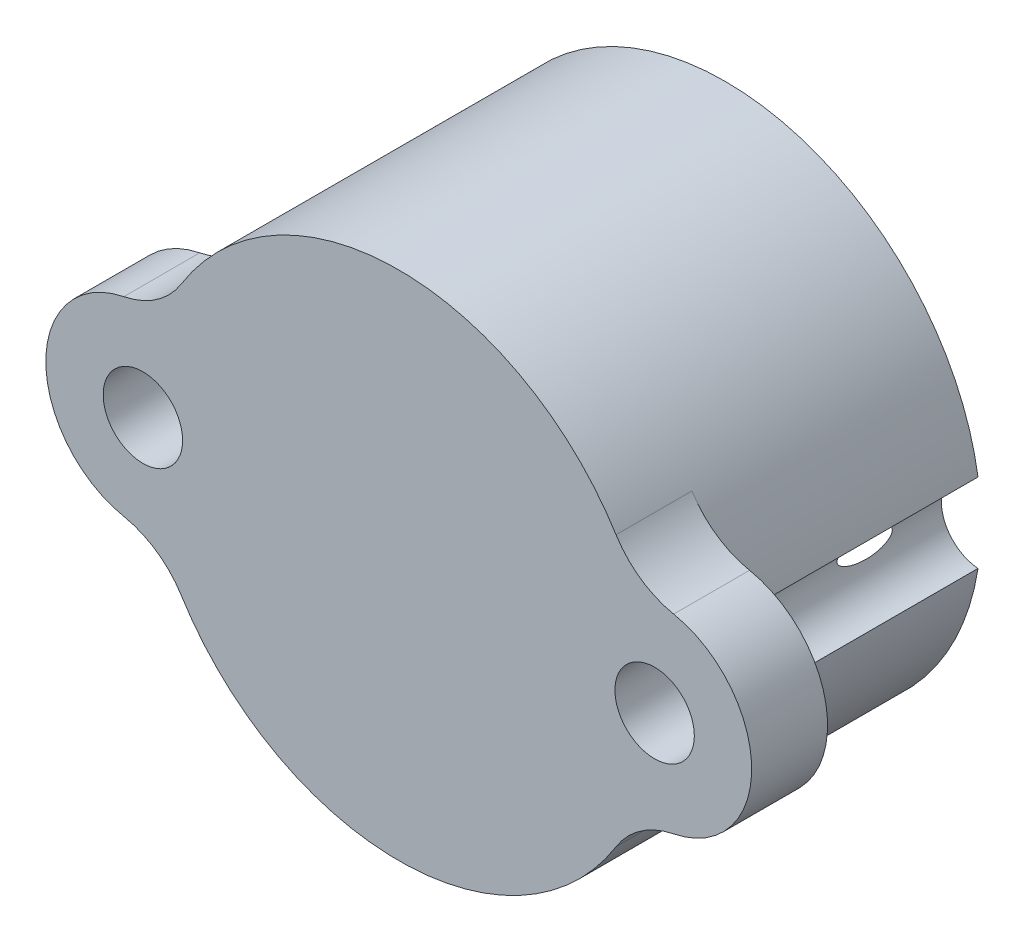
SolidWorks part; units mm, degrees
material "Natural Rubber"
ref_plane "Plan de face" through (0, 0, 0) normal (0, 0, 1) x (1, 0, 0)
ref_plane "Plan de dessus" through (0, 0, 0) normal (0, 1, 0) x (1, 0, 0)
ref_plane "Plan de droite" through (0, 0, 0) normal (1, 0, 0) x (0, 0, -1)
sketch "Esquisse1" plane through (0, 0, 0) normal (0, 0, 1) x (1, 0, 0)
  circle A0 centre (0, 0) radius 7.366
  dimension "D1" = 14.732
extrude "Boss.-Extru.1" add sketch "Esquisse1" along normal blind 9.398
sketch "Esquisse2" plane through (0, 0, 9.398) normal (0, 0, 1) x (1, 0, 0)
  line L0 (-7.366, 0) -> (7.366, 0) construction
  line L1 (-7.366, 2.794) -> (7.366, 2.794)
  line L2 (-7.366, -2.794) -> (7.366, -2.794)
  line L3 (-10.16, 0) -> (10.16, 0)
  arc A0 (-7.366, 2.794) -> (-7.366, -2.794) centre (-7.366, 0) ccw
  arc A1 (7.366, -2.794) -> (7.366, 2.794) centre (7.366, 0) ccw
  point P2 (0, 0)
  point P7 (0, 0)
  circle M3 centre (0, 0) radius 7.366
  dimension "D2" = 20.32
  dimension "D1" = 14.732
extrude "Boss.-Extru.2" add sketch "Esquisse2" against normal blind 2.1844 contours L3 A1 L1 M3 | L2 A1 L3 M3 | L3 A0 L2 M3 | L1 A0 L3 M3 region at (-8.4491, 1.2554, 9.398) region at (-8.4491, -1.2554, 9.398) region at (8.4491, 1.2554, 9.398) region at (8.4491, -1.2554, 9.398)
fillet "Congé1" radius 2.54 4 edges at (6.8155, 2.794, 8.3058) (6.8155, -2.794, 8.3058) (-6.8155, -2.794, 8.3058) (-6.8155, 2.794, 8.3058)
sketch "Esquisse3" plane through (0, 0, 9.398) normal (0, 0, 1) x (1, 0, 0)
  line L0 (-7.366, 0) -> (7.366, 0)
  circle A0 centre (-7.366, 0) radius 1.143
  circle A1 centre (7.366, 0) radius 1.143
  point P4 (0, 0)
  dimension "D2" = 2.286
  dimension "D3" = 2.286
  dimension "D1" = 14.732
extrude "Enlèv. mat.-Extru.2" cut sketch "Esquisse3" against normal through all contours A0 | A1 region at (-8.4767, 0, 9.398)
sketch "Esquisse4" plane through (0, 0, 0) normal (1, 0, 0) x (0, 0, -1)
  line L2 (-7.0373, 0) -> (7.1163, 0) construction
  line L3 (-8.4836, 0) -> (4.064, 0)
  line L4 (-9.398, -3.8892) -> (-9.398, -7.366) construction
  arc A0 (4.064, 0) -> (-8.4836, 0) centre (-2.2098, 0) ccw
  dimension "D1" = 12.5476
  dimension "D2" = 13.462
revolve "Cut-Revolve1" cut sketch "Esquisse4" angle 360 about L2
